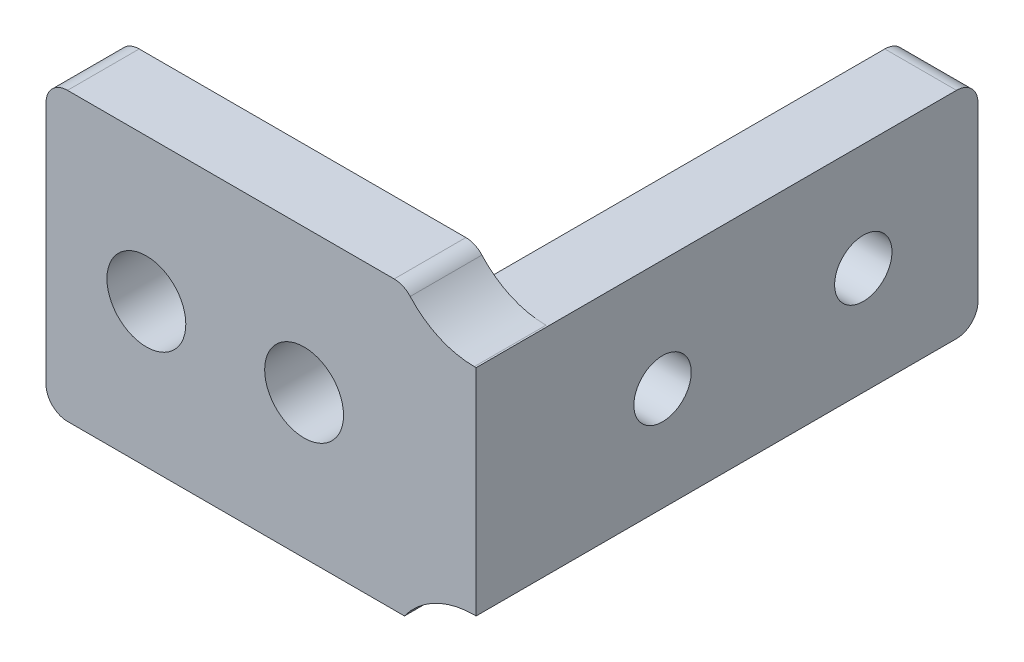
SolidWorks part; units mm, degrees
ref_plane "Front Plane" through (0, 0, 0) normal (0, 0, 1) x (1, 0, 0)
ref_plane "Top Plane" through (0, 0, 0) normal (0, 1, 0) x (1, 0, 0)
ref_plane "Right Plane" through (0, 0, 0) normal (1, 0, 0) x (0, 0, -1)
sketch "Sketch4" plane through (0, 0, 0) normal (0, 0, 1) x (1, 0, 0)
  line L0 (0, 0) -> (5, 0) construction
  line L5 (25, -10) -> (-25, -10)
  line L6 (25, -10) -> (25, 10)
  line L7 (25, 10) -> (-25, 10)
  line L8 (-25, -10) -> (-25, 10)
  line L9 (25, -10) -> (-25, 10) construction
  line L10 (25, 10) -> (-25, -10) construction
  line L11 (5, 7.5) -> (5, -7.5)
  line L12 (5, 7.5) -> (0, 7.5)
  line L13 (0, 7.5) -> (0, 10)
  line L14 (5, -7.5) -> (0, -7.5)
  line L15 (0, -7.5) -> (0, -10)
  point P0 (0, 0)
  point P1 (0, 0)
  point P12 (5, 0)
  dimension "D1" = 20
  dimension "D2" = 50
  dimension "D3" = 5
  dimension "D4" = 15
extrude "Boss-Extrude1" add sketch "Sketch4" along normal blind 5 contours L15 L14 L11 L12 L13 L7 L8 L5 region at (-10.5435, 0, 0)
sketch "Sketch7" plane through (0, 0, 0) normal (0, 0, -1) x (-1, 0, 0)
  line L0 (-5, 7.5) -> (0, 7.5)
  line L1 (0, 7.5) -> (0, -7.5)
  line L2 (0, -7.5) -> (-5, -7.5)
  line L3 (-5, -7.5) -> (0, -7.5) construction
  line L4 (-5, -7.5) -> (-5, 7.5)
extrude "Boss-Extrude2" add sketch "Sketch7" along normal blind 30
sketch "Sketch9" plane through (0, 0, 0) normal (0, 0, -1) x (-1, 0, 0)
  line L0 (0, 0) -> (7, 0) construction
  line L1 (0, -7.5) -> (0, 7.5) construction
  line L2 (25, 0) -> (18, 0) construction
  line L3 (25, -10) -> (25, 10) construction
  point P1 (7, 0)
  point P5 (18, 0)
  dimension "D1" = 7
sketch "Sketch11" plane through (0, 0, 0) normal (-1, 0, 0) x (0, 0, 1)
  line L0 (-30, 0) -> (-22, 0) construction
  line L1 (-30, -7.5) -> (-30, 7.5) construction
  line L2 (0, 0) -> (-8, 0) construction
  point P1 (-22, 0)
  point P10 (-8, -0.2713)
  dimension "D1" = 8
hole_wizard "Ø4.0 (4) Diameter Hole1" positions "Sketch11" profile "Sketch12" hole size "Ø4.0" standard "ANSI Metric" end condition up to next
sketch "Sketch12" plane through (0, -0.2713, -8) normal (0, 1, 0) x (0, 0, 1)
  line L0 (0, 0) -> (0, 5)
  line L1 (0, 5) -> (2, 5)
  line L2 (2, 5) -> (2, 0.3018)
  line L3 (2, 0.3018) -> (2.125, 0)
  line L5 (2.125, 0) -> (0, 0)
  line L6 (-2, 0.3018) -> (-2.125, 0) construction
  line L11 (0, -6.35) -> (0, 107.95) construction
  dimension "Thru Hole Dia." = 4
  dimension "Thru Hole Depth" = 5
  dimension "Near C'Sink Dia." = 4.25
  dimension "Near C'Sink Angle" = 45
hole_wizard "Ø5.5 (5.5) Diameter Hole1" positions "Sketch9" profile "Sketch13" hole size "Ø5.5" standard "ANSI Metric" end condition up to next
sketch "Sketch13" plane through (-18, 0, 0) normal (1, 0, 0) x (0, 1, 0)
  line L0 (0, 0) -> (0, 5)
  line L1 (0, 5) -> (2.75, 5)
  line L2 (2.75, 5) -> (2.75, 0.3018)
  line L3 (2.75, 0.3018) -> (2.875, 0)
  line L5 (2.875, 0) -> (0, 0)
  line L6 (-2.75, 0.3018) -> (-2.875, 0) construction
  line L11 (0, -6.35) -> (0, 107.95) construction
  dimension "Thru Hole Dia." = 5.5
  dimension "Thru Hole Depth" = 5
  dimension "Near C'Sink Dia." = 5.75
  dimension "Near C'Sink Angle" = 45
fillet "Fillet1" radius 6 2 edges at (0, -7.5, 2.5) (0, 7.5, 2.5)
fillet "Fillet2" radius 1.5 5 edges at (2.5, -7.5, -30) (2.5, 7.5, -30) (0, 10, 2.5) (-25, 10, 2.5) (-25, -10, 2.5)
